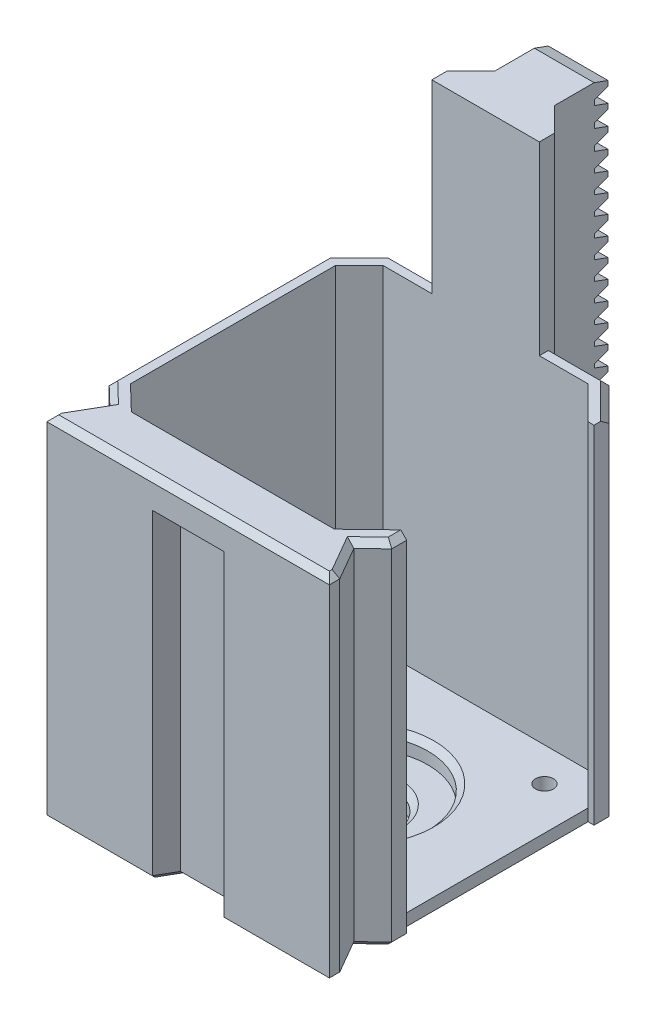
SolidWorks part; units mm, degrees
ref_plane "Front Plane" through (0, 0, 0) normal (0, 0, 1) x (1, 0, 0)
ref_plane "Top Plane" through (0, 0, 0) normal (0, 1, 0) x (1, 0, 0)
ref_plane "Right Plane" through (0, 0, 0) normal (1, 0, 0) x (0, 0, -1)
sketch "Sketch1" plane through (0, 0, 0) normal (0, 1, 0) x (1, 0, 0)
  line L0 (-21.15, 17.15) -> (-17.15, 21.15)
  line L1 (-17, -21.15) -> (17, -21.15)
  line L2 (-21.15, -17.15) -> (-21.15, 17.15)
  line L3 (-17.15, 21.15) -> (17.15, 21.15)
  line L4 (21.15, -17.15) -> (21.15, 17.15)
  line L5 (-21.15, -21.15) -> (21.15, 21.15) construction
  line L6 (-21.15, 21.15) -> (21.15, -21.15) construction
  line L7 (-21.15, -17.15) -> (-17, -21.15)
  line L8 (17, -21.15) -> (21.15, -17.15)
  line L9 (17.15, 21.15) -> (21.15, 17.15)
  circle A0 centre (-15.5, 15.5) radius 1.5
  circle A1 centre (15.5, 15.5) radius 1.5
  circle A2 centre (15.5, -15.5) radius 1.5
  circle A3 centre (-15.5, -15.5) radius 1.5
  circle A4 centre (0, 0) radius 11.5
  point P0 (0, 0)
  dimension "D3" = 3
  dimension "D4" = 3
  dimension "D9" = 3
  dimension "D10" = 3
  dimension "D12" = 23
  dimension "D1" = 42.3
  dimension "D2" = 42.3
  dimension "D11" = 31
  dimension "D13" = 34
  dimension "D6" = 4
  dimension "D7" = 4
extrude "Mount Face Extrude" add sketch "Sketch1" along normal blind 3
chamfer "Bracket Mount Hole Chamfer" distance 0.75 angle 45 4 edges at (-15.5, 0, -14) (15.5, 0, -14) (15.5, 0, 17) (-15.5, 0, 17)
sketch "Sketch5" plane through (0, 0, 0) normal (0, 1, 0) x (1, 0, 0)
  line L0 (21.15, -17.15) -> (22.65, -15.7042)
  line L1 (23.65, -14.7404) -> (23.65, 14.65) construction
  line L3 (-24.65, -28.65) -> (24.65, -28.65) construction
  line L5 (-23.65, -26.9179) -> (-23.65, -28.65)
  line L6 (-23.65, -28.65) -> (23.65, -28.65)
  line L7 (23.65, -28.65) -> (23.65, -26.9179)
  line L8 (-23.65, -26.9179) -> (-24.65, -28.65) construction
  line L9 (24.65, -28.65) -> (23.65, -26.9179) construction
  line L10 (22.65, 15.65) -> (23.65, 15.65)
  line L11 (22.65, -15.7042) -> (23.65, -15.7042)
  line L12 (23.65, 14.65) -> (23.65, 15.65) construction
  line L13 (22.65, 15.65) -> (23.65, 14.65) construction
  line L14 (23.65, -15.7042) -> (23.65, -14.7404) construction
  line L15 (22.65, -15.7042) -> (23.65, -14.7404) construction
  line L16 (-23.65, 18.1855) -> (-23.65, -18.2126)
  line L17 (-23.65, -18.2126) -> (-18.0087, -23.65)
  line L18 (-18.0087, -23.65) -> (18.0087, -23.65)
  line L19 (18.0087, -23.65) -> (23.65, -18.2126)
  line L20 (23.65, -18.2126) -> (23.65, 18.1855)
  line L21 (23.65, 18.1855) -> (18.1855, 23.65)
  line L22 (18.1855, 23.65) -> (-18.1855, 23.65)
  line L23 (-18.1855, 23.65) -> (-23.65, 18.1855)
  line L24 (-23.65, 14.65) -> (-23.65, -18.2126)
  line L25 (-23.65, -18.2126) -> (-20.4209, -21.325)
  line L26 (-18.0087, -23.65) -> (18.0087, -23.65) construction
  line L27 (20.4209, -21.325) -> (23.65, -18.2126)
  line L28 (23.65, -18.2126) -> (23.65, -15.7042)
  line L29 (23.65, 18.1855) -> (18.1855, 23.65)
  line L30 (18.1855, 23.65) -> (-18.1855, 23.65)
  line L31 (-18.1855, 23.65) -> (-23.65, 18.1855)
  line L32 (-21.15, 17.15) -> (-23.65, 14.65) construction
  line L33 (21.15, 17.15) -> (22.65, 15.65)
  line L34 (-23.65, 18.1855) -> (-23.65, 14.65)
  line L35 (23.65, 15.65) -> (23.65, 18.1855)
  line L36 (-23.65, -26.9179) -> (-20.4209, -21.325)
  line L38 (20.4209, -21.325) -> (23.65, -26.9179)
  line L40 (-21.15, 17.15) -> (-21.15, -17.15)
  line L41 (-21.15, -17.15) -> (-17, -21.15)
  line L42 (-17, -21.15) -> (17, -21.15)
  line L43 (17, -21.15) -> (21.15, -17.15)
  line L44 (21.15, -17.15) -> (21.15, 17.15)
  line L45 (21.15, 17.15) -> (17.15, 21.15)
  line L46 (17.15, 21.15) -> (-17.15, 21.15)
  line L47 (-17.15, 21.15) -> (-21.15, 17.15)
  line L48 (-21.15, 17.15) -> (-21.15, -17.15)
  line L49 (-21.15, -17.15) -> (-17, -21.15)
  line L50 (-17, -21.15) -> (17, -21.15)
  line L51 (17, -21.15) -> (21.15, -17.15)
  line L52 (21.15, -17.15) -> (21.15, 17.15) construction
  line L53 (21.15, 17.15) -> (17.15, 21.15)
  line L54 (17.15, 21.15) -> (-17.15, 21.15)
  line L55 (-17.15, 21.15) -> (-21.15, 17.15)
  line L60 (-20.4209, -21.325) -> (-18.0087, -23.65) construction
  line L61 (18.0087, -23.65) -> (20.4209, -21.325) construction
  point P32 (0, -28.65)
  dimension "D3" = 47.3
  dimension "D4" = 60
  dimension "D5" = 47.3
  dimension "D6" = 1
  dimension "D7" = 5
  dimension "D8" = 1
  dimension "D1" = 2.5
  dimension "D2" = 0
extrude "Main Body Extrude" add sketch "Sketch5" along normal blind 59
sketch "Sketch37" plane through (0, 0, 0) normal (0, -1, 0) x (1, 0, 0)
  line L0 (21.15, -17.15) -> (22.65, -15.65) construction
  line L1 (21.15, 17.15) -> (21.15, -17.15) construction
  line L2 (22.65, 15.7042) -> (21.15, 17.15) construction
  line L3 (21.15, -17.15) -> (22.65, -15.65)
  line L4 (21.15, 17.15) -> (21.15, -17.15)
  line L5 (22.65, 15.7042) -> (21.15, 17.15)
  line L6 (22.65, 15.7042) -> (22.65, -15.65)
extrude "Front Face Fill in Extrude" add sketch "Sketch37" against normal up to surface (3 mm away) up to face at (0, 3, 0)
sketch "Sketch39" plane through (0, 0, 0) normal (0, -1, 0) x (1, 0, 0)
  line L0 (-6, 28.65) -> (-4.2679, 25.65)
  line L1 (-23.65, 28.65) -> (23.65, 28.65) construction
  line L2 (-4.2679, 25.65) -> (4.2679, 25.65)
  line L3 (4.2679, 25.65) -> (6, 28.65)
  line L4 (6, 28.65) -> (-6, 28.65)
  line L5 (0, 0) -> (0, 25.65) construction
  dimension "D1" = 3
  dimension "D2" = 12
  dimension "D3" = 60
extrude "Limit Tab" cut sketch "Sketch39" against normal offset from surface (54 mm away) 5 up to face at (2.2864, 59, 4.8477)
sketch "Sketch13" plane through (0, 0, 0) normal (1, 0, 0) x (0, 0, -1)
  line L0 (36.65, 6.9244) -> (36.65, 6.0816)
  line L1 (36.65, 6.0816) -> (34.4, 5.2626)
  line L2 (34.4, 5.2626) -> (34.4, 4.6018)
  line L3 (34.4, 4.6018) -> (36.65, 3.7828)
  line L4 (36.65, 10.066) -> (36.65, 9.2232)
  line L5 (36.65, 9.2232) -> (34.4, 8.4042)
  line L6 (34.4, 8.4042) -> (34.4, 7.7434)
  line L7 (34.4, 7.7434) -> (36.65, 6.9244)
  line L8 (36.65, 13.2076) -> (36.65, 12.3648)
  line L9 (36.65, 12.3648) -> (34.4, 11.5458)
  line L10 (34.4, 11.5458) -> (34.4, 10.885)
  line L11 (34.4, 10.885) -> (36.65, 10.066)
  line L12 (36.65, 16.3492) -> (36.65, 15.5064)
  line L13 (36.65, 15.5064) -> (34.4, 14.6874)
  line L14 (34.4, 14.6874) -> (34.4, 14.0266)
  line L15 (34.4, 14.0266) -> (36.65, 13.2076)
  line L16 (36.65, 19.4908) -> (36.65, 18.648)
  line L17 (36.65, 18.648) -> (34.4, 17.829)
  line L18 (34.4, 17.829) -> (34.4, 17.1681)
  line L19 (34.4, 17.1681) -> (36.65, 16.3492)
  line L20 (36.65, 22.6324) -> (36.65, 21.7895)
  line L21 (36.65, 21.7895) -> (34.4, 20.9706)
  line L22 (34.4, 20.9706) -> (34.4, 20.3097)
  line L23 (34.4, 20.3097) -> (36.65, 19.4908)
  line L24 (36.65, 25.774) -> (36.65, 24.9311)
  line L25 (36.65, 24.9311) -> (34.4, 24.1122)
  line L26 (34.4, 24.1122) -> (34.4, 23.4513)
  line L27 (34.4, 23.4513) -> (36.65, 22.6324)
  line L28 (36.65, 28.9156) -> (36.65, 28.0727)
  line L29 (36.65, 28.0727) -> (34.4, 27.2538)
  line L30 (34.4, 27.2538) -> (34.4, 26.5929)
  line L31 (34.4, 26.5929) -> (36.65, 25.774)
  line L32 (36.65, 32.0572) -> (36.65, 31.2143)
  line L33 (36.65, 31.2143) -> (34.4, 30.3954)
  line L34 (34.4, 30.3954) -> (34.4, 29.7345)
  line L35 (34.4, 29.7345) -> (36.65, 28.9156)
  line L36 (36.65, 35.1988) -> (36.65, 34.3559)
  line L37 (36.65, 34.3559) -> (34.4, 33.537)
  line L38 (34.4, 33.537) -> (34.4, 32.8761)
  line L39 (34.4, 32.8761) -> (36.65, 32.0572)
  line L40 (36.65, 38.3404) -> (36.65, 37.4975)
  line L41 (36.65, 37.4975) -> (34.4, 36.6786)
  line L42 (34.4, 36.6786) -> (34.4, 36.0177)
  line L43 (34.4, 36.0177) -> (36.65, 35.1988)
  line L44 (36.65, 41.482) -> (36.65, 40.6391)
  line L45 (36.65, 40.6391) -> (34.4, 39.8202)
  line L46 (34.4, 39.8202) -> (34.4, 39.1593)
  line L47 (34.4, 39.1593) -> (36.65, 38.3404)
  line L48 (36.65, 44.6235) -> (36.65, 43.7807)
  line L49 (36.65, 43.7807) -> (34.4, 42.9618)
  line L50 (34.4, 42.9618) -> (34.4, 42.3009)
  line L51 (34.4, 42.3009) -> (36.65, 41.482)
  line L52 (36.65, 47.7651) -> (36.65, 46.9223)
  line L53 (36.65, 46.9223) -> (34.4, 46.1034)
  line L54 (34.4, 46.1034) -> (34.4, 45.4425)
  line L55 (34.4, 45.4425) -> (36.65, 44.6235)
  line L56 (36.65, 50.9067) -> (36.65, 50.0639)
  line L57 (36.65, 50.0639) -> (34.4, 49.2449)
  line L58 (34.4, 49.2449) -> (34.4, 48.5841)
  line L59 (34.4, 48.5841) -> (36.65, 47.7651)
  line L60 (36.65, 54.0483) -> (36.65, 53.2055)
  line L61 (36.65, 53.2055) -> (34.4, 52.3865)
  line L62 (34.4, 52.3865) -> (34.4, 51.7257)
  line L63 (34.4, 51.7257) -> (36.65, 50.9067)
  line L64 (36.65, 57.1899) -> (36.65, 56.3471)
  line L65 (36.65, 56.3471) -> (34.4, 55.5281)
  line L66 (34.4, 55.5281) -> (34.4, 54.8673)
  line L67 (34.4, 54.8673) -> (36.65, 54.0483)
  line L68 (36.65, 60.3315) -> (36.65, 59.4887)
  line L69 (36.65, 59.4887) -> (34.4, 58.6697)
  line L70 (34.4, 58.6697) -> (34.4, 58.0089)
  line L71 (34.4, 58.0089) -> (36.65, 57.1899)
  line L72 (36.65, 63.4731) -> (36.65, 62.6302)
  line L73 (36.65, 62.6302) -> (34.4, 61.8113)
  line L74 (34.4, 61.8113) -> (34.4, 61.1504)
  line L75 (34.4, 61.1504) -> (36.65, 60.3315)
  line L76 (36.65, 66.6147) -> (36.65, 65.7718)
  line L77 (36.65, 65.7718) -> (34.4, 64.9529)
  line L78 (34.4, 64.9529) -> (34.4, 64.292)
  line L79 (34.4, 64.292) -> (36.65, 63.4731)
  line L80 (36.65, 69.7563) -> (36.65, 68.9134)
  line L81 (36.65, 68.9134) -> (34.4, 68.0945)
  line L82 (34.4, 68.0945) -> (34.4, 67.4336)
  line L83 (34.4, 67.4336) -> (36.65, 66.6147)
  line L84 (36.65, 72.8979) -> (36.65, 72.055)
  line L85 (36.65, 72.055) -> (34.4, 71.2361)
  line L86 (34.4, 71.2361) -> (34.4, 70.5752)
  line L87 (34.4, 70.5752) -> (36.65, 69.7563)
  line L88 (36.65, 76.0395) -> (36.65, 75.1966)
  line L89 (36.65, 75.1966) -> (34.4, 74.3777)
  line L90 (34.4, 74.3777) -> (34.4, 73.7168)
  line L91 (34.4, 73.7168) -> (36.65, 72.8979)
  line L92 (36.65, 79.1811) -> (36.65, 78.3382)
  line L93 (36.65, 78.3382) -> (34.4, 77.5193)
  line L94 (34.4, 77.5193) -> (34.4, 76.8584)
  line L95 (34.4, 76.8584) -> (36.65, 76.0395)
  line L98 (36.65, 3.7828) -> (36.65, 2.94)
  line L99 (36.65, 2.94) -> (34.4, 2.1211)
  line L100 (34.4, 2.1211) -> (34.4, 1.4602)
  line L101 (34.4, 1.4602) -> (36.65, 0.6413)
  line L102 (36.65, 0.6413) -> (36.65, 0)
  line L103 (36.65, 0) -> (23.65, 0)
  line L104 (23.65, 0) -> (23.65, 90)
  line L105 (23.65, 59) -> (23.65, 0) construction
  line L108 (34.4, 80) -> (36.65, 79.1811)
  line L146 (36.65, 82.5046) -> (36.65, 81.6618)
  line L147 (18.1855, 0) -> (23.65, 0) construction
  line L148 (34.4, 80.6609) -> (34.4, 80) [skipped]
  line L149 (36.65, 81.4798) -> (34.4, 80.6609) [skipped]
  line L150 (36.65, 82.3227) -> (36.65, 81.4798) [skipped]
  line L151 (34.4, 83.1416) -> (36.65, 82.3227) [skipped]
  line L152 (36.65, 84.6214) -> (34.4, 83.8025) [skipped]
  line L153 (34.4, 86.2832) -> (36.65, 85.4643) [skipped]
  line L154 (36.65, 87.763) -> (34.4, 86.9441) [skipped]
  line L155 (34.4, 89.4248) -> (36.65, 88.6058) [skipped]
  line L156 (36.65, 90.9046) -> (34.4, 90.0856) [skipped]
  line L157 (34.4, 92.5664) -> (36.65, 91.7474) [skipped]
  line L158 (34.4, 83.8025) -> (34.4, 83.1416) [skipped]
  line L159 (34.4, 86.9441) -> (34.4, 86.2832) [skipped]
  line L160 (36.65, 85.4643) -> (36.65, 84.6214) [skipped]
  line L161 (36.65, 88.6058) -> (36.65, 87.763) [skipped]
  line L162 (34.4, 90.0856) -> (34.4, 89.4248) [skipped]
  line L163 (36.65, 91.7474) -> (36.65, 90.9046) [skipped]
  line L164 (34.4, 93.2272) -> (34.4, 92.5664) [skipped]
  line L165 (36.65, 94.0462) -> (34.4, 93.2272) [skipped]
  line L166 (36.65, 94.889) -> (36.65, 94.0462) [skipped]
  line L167 (34.4, 95.708) -> (36.65, 94.889) [skipped]
  line L168 (34.4, 96.3688) -> (34.4, 95.708) [skipped]
  line L169 (36.65, 97.1878) -> (34.4, 96.3688) [skipped]
  line L170 (36.65, 98.0306) -> (36.65, 97.1878) [skipped]
  line L171 (34.4, 98.8496) -> (36.65, 98.0306) [skipped]
  line L172 (34.4, 99.5104) -> (34.4, 98.8496) [skipped]
  line L173 (36.65, 100.3294) -> (34.4, 99.5104) [skipped]
  line L174 (36.65, 101.1722) -> (36.65, 100.3294) [skipped]
  line L175 (34.4, 101.9911) -> (36.65, 101.1722) [skipped]
  line L176 (34.4, 102.652) -> (34.4, 101.9911) [skipped]
  line L177 (36.65, 110.597) -> (36.65, 109.7541) [skipped]
  line L178 (36.65, 109.7541) -> (34.4, 108.9352) [skipped]
  line L179 (34.4, 108.9352) -> (34.4, 108.2743) [skipped]
  line L180 (34.4, 108.2743) -> (36.65, 107.4554) [skipped]
  line L181 (36.65, 107.4554) -> (36.65, 106.6125) [skipped]
  line L182 (36.65, 106.6125) -> (34.4, 105.7936) [skipped]
  line L183 (34.4, 105.7936) -> (34.4, 105.1327) [skipped]
  line L184 (34.4, 105.1327) -> (36.65, 104.3138) [skipped]
  line L185 (36.65, 104.3138) -> (36.65, 103.471) [skipped]
  line L186 (36.65, 103.471) -> (34.4, 102.652) [skipped]
  line L187 (36.65, 81.6618) -> (34.4, 80.8429)
  line L188 (34.4, 80.8429) -> (34.4, 80)
  line L189 (36.65, 85.8282) -> (36.65, 84.9854)
  line L190 (36.65, 84.9854) -> (34.4, 84.1664)
  line L191 (34.4, 84.1664) -> (34.4, 83.3236)
  line L192 (34.4, 83.3236) -> (36.65, 82.5046)
  line L193 (36.65, 89.1518) -> (36.65, 88.3089)
  line L194 (36.65, 88.3089) -> (34.4, 87.49)
  line L195 (34.4, 87.49) -> (34.4, 86.6472)
  line L196 (34.4, 86.6472) -> (36.65, 85.8282)
  line L200 (34.4, 89.9707) -> (36.65, 89.1518)
  line L210 (23.65, 90) -> (34.3196, 90)
  line L211 (34.4, 89.9707) -> (34.3196, 90)
  point P14 (23.65, 90)
  dimension "D1" = 90
  dimension "D2" = 0.8429
  dimension "D3" = 0.6609
  dimension "D4" = 2.2987
  dimension "D5" = 13
  dimension "D6" = 0.6413
  dimension "D7" = 20
  dimension "D8" = 3.1416
  dimension "D9" = 35
extrude "Rack Extrude" add sketch "Sketch13" against normal mid plane 10
sketch "Rack Line" plane through (0, 0, 0) normal (1, 0, 0) x (0, 0, -1)
  line L0 (35.65, 0) -> (35.65, 90)
  line L1 (23.65, 0) -> (36.65, 0) construction
  line L3 (23.65, 59) -> (23.65, 0) construction
  dimension "D1" = 12
chamfer "Rack Chamfer" distance 4 angle 45 2 edges at (5, 29.5, -23.65) (-5, 29.5, -23.65)
sketch "Sketch15" plane through (0, 59, 0) normal (0, 1, 0) x (1, 0, 0)
  line L0 (-5, 27.65) -> (-9, 23.65)
  line L1 (17.15, 21.15) -> (-17.15, 21.15) construction
  line L2 (-9, 21.15) -> (9, 21.15)
  line L3 (9, 23.65) -> (5, 27.65)
  line L4 (5, 27.65) -> (-5, 27.65)
  line L5 (9, 23.65) -> (5, 27.65) construction
  line L6 (-5, 27.65) -> (-9, 23.65) construction
  line L9 (-9, 23.65) -> (-9, 21.15)
  line L10 (9, 23.65) -> (9, 21.15)
  line L11 (-11.5, 21.15) -> (-9, 21.15) construction
  line L12 (-9, 23.65) -> (-11.5, 21.15) construction
  line L13 (9, 21.15) -> (11.5, 21.15) construction
  line L14 (11.5, 21.15) -> (9, 23.65) construction
  line L15 (-9, 23.65) -> (-18.1855, 23.65) construction
  line L16 (-5, 27.65) -> (-5, 36.65) construction
extrude "Rack Support Base Extrude" add sketch "Sketch15" along normal up to surface (31 mm away) up to face at (0, 90, -28.9848)
sketch "Sketch27" plane through (0, 0, 0) normal (0, -1, 0) x (-1, 0, 0)
  circle A4 centre (0, 0) radius 13.6
  circle A5 centre (0, 0) radius 11.5 construction
  circle A6 centre (0, 0) radius 11.5
  circle A7 centre (0, 0) radius 6
  circle M47 centre (0, 0) radius 11.5
  dimension "D1" = 12
  dimension "D4" = 27.2
extrude "Face Cosmetic Ring Extrude" add sketch "Sketch27" along normal blind 4 contours A4 M47 | A7 M47 region at (13.2153, 0, 0) region at (11.1747, 0, 0)
chamfer "Face Cosmetic Ring Main Chamfer" distance 4 angle 45 1 edges at (0, 0, -13.6)
chamfer "Face Cosmetic Ring Main Through Hole Chamfer" distance 1 angle 45 3 edges at (0, -4, -6) (0, 0, -6) (0, 3, 11.5)
chamfer "Front/Back Face Chamfer" distance 1 angle 45 36 edges at (13.5928, 59, -23.65) (20.9178, 59, -20.9178) (23.65, 59, 16.9584) (22.0354, 59, 19.7688) (0, 59, 28.65) (-22.0354, 59, 19.7688) (-23.65, 59, 0.0135) (-20.9178, 59, -20.9178) (-13.5928, 59, -23.65) (-7, 0, -25.65) (-13.5928, 0, -23.65) (-20.9178, 0, -20.9178) (7, 0, -25.65) (13.5928, 0, -23.65) (20.9178, 0, -20.9178) (23.65, 0, -16.9178) (23.15, 0, -15.65) (22.65, 0, 0.0271) (23.15, 0, 15.7042) (23.65, 0, 16.9584) (22.0354, 0, 19.7688) (14.825, 0, 28.65) (5.134, 0, 27.15) (0, 0, 25.65) (-5.134, 0, 27.15) (-14.825, 0, 28.65) (-22.0354, 0, 19.7688) (-23.65, 0, 0.0135) (23.65, 59, 27.784) (-23.65, 59, 27.784) (23.65, 0, 27.784) (-23.65, 0, 27.784) (22.0354, 0, 24.1215) (-22.0354, 0, 24.1215) (22.0354, 59, 24.1215) (-22.0354, 59, 24.1215)
